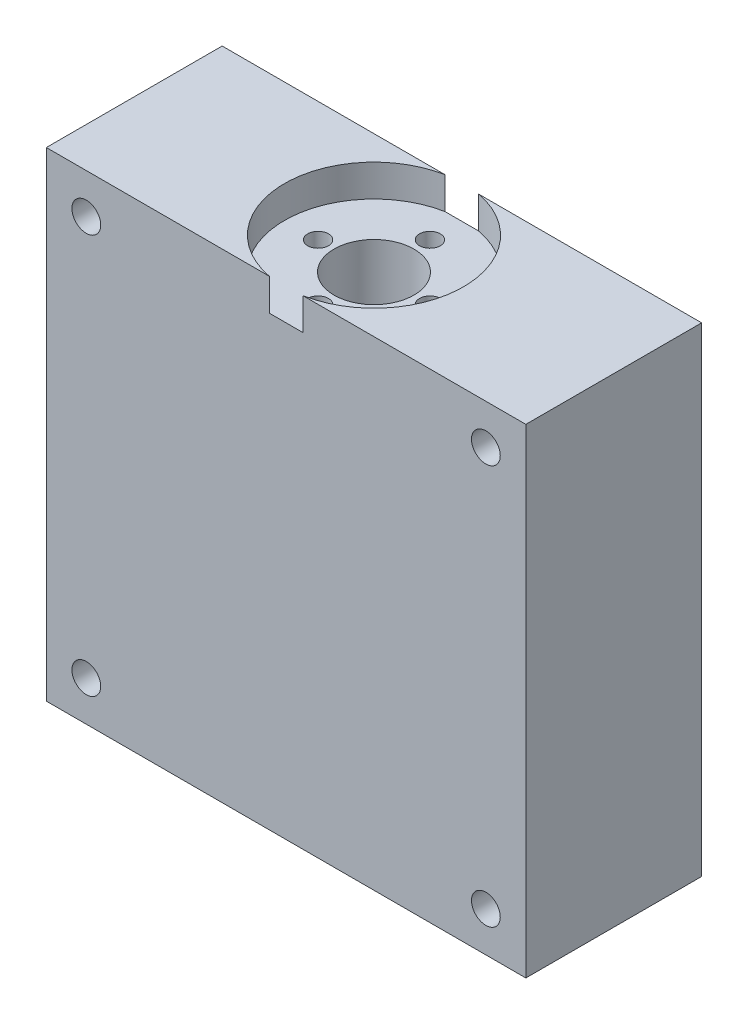
SolidWorks part; units mm, degrees
ref_plane "Front Plane" through (0, 0, 0) normal (0, 0, 1) x (1, 0, 0)
ref_plane "Top Plane" through (0, 0, 0) normal (0, 1, 0) x (1, 0, 0)
ref_plane "Right Plane" through (0, 0, 0) normal (1, 0, 0) x (0, 0, -1)
sketch "Sketch1" plane through (0, 0, 0) normal (0, 0, 1) x (1, 0, 0)
  line L1 (-30, 30) -> (30, 30)
  line L2 (-30, 30) -> (-30, -30)
  line L3 (-30, -30) -> (30, -30)
  line L4 (30, 30) -> (30, -30)
  line L5 (-30, 30) -> (30, -30) construction
  line L6 (-30, -30) -> (30, 30) construction
  line L7 (-25, -25) -> (25, -25) construction
  line L8 (-25, -25) -> (-25, 25) construction
  line L9 (-25, 25) -> (25, 25) construction
  line L10 (25, -25) -> (25, 25) construction
  line L11 (-25, -25) -> (25, 25) construction
  line L12 (-25, 25) -> (25, -25) construction
  circle A0 centre (-25, 25) radius 1.8
  circle A1 centre (25, 25) radius 1.8
  circle A2 centre (25, -25) radius 1.8
  circle A3 centre (-25, -25) radius 1.8
  point P0 (0, 0)
  point P6 (0, 0)
  dimension "D1" = 60
  dimension "D2" = 60
  dimension "D3" = 50
  dimension "D4" = 50
extrude "Boss-Extrude1" add sketch "Sketch1" along normal blind 22
sketch "Sketch2" plane through (0, 30, 0) normal (0, 1, 0) x (1, 0, 0)
  line L0 (30, 0) -> (-30, 0) construction
  circle A0 centre (0, -11) radius 11.2
  dimension "D1" = 11
extrude "Cut-Extrude1" cut sketch "Sketch2" against normal blind 4
sketch "Sketch3" plane through (0, 26, 0) normal (0, 1, 0) x (1, 0, 0)
  circle A0 centre (0, -11) radius 5
extrude "Cut-Extrude2" cut sketch "Sketch3" against normal up to next
sketch "Sketch4" plane through (0, -30, 0) normal (0, -1, 0) x (1, 0, 0)
  circle A0 centre (0, 11) radius 7.2
extrude "Cut-Extrude3" cut sketch "Sketch4" against normal blind 46
sketch "Sketch5" plane through (0, 26, 0) normal (0, 1, 0) x (1, 0, 0)
  circle A0 centre (0, -11) radius 7 construction
  circle A1 centre (0, -4) radius 1.3
  circle A2 centre (7, -11) radius 1.3
  circle A3 centre (0, -18) radius 1.3
  circle A4 centre (-7, -11) radius 1.3
extrude "Cut-Extrude4" cut sketch "Sketch5" against normal blind 6
